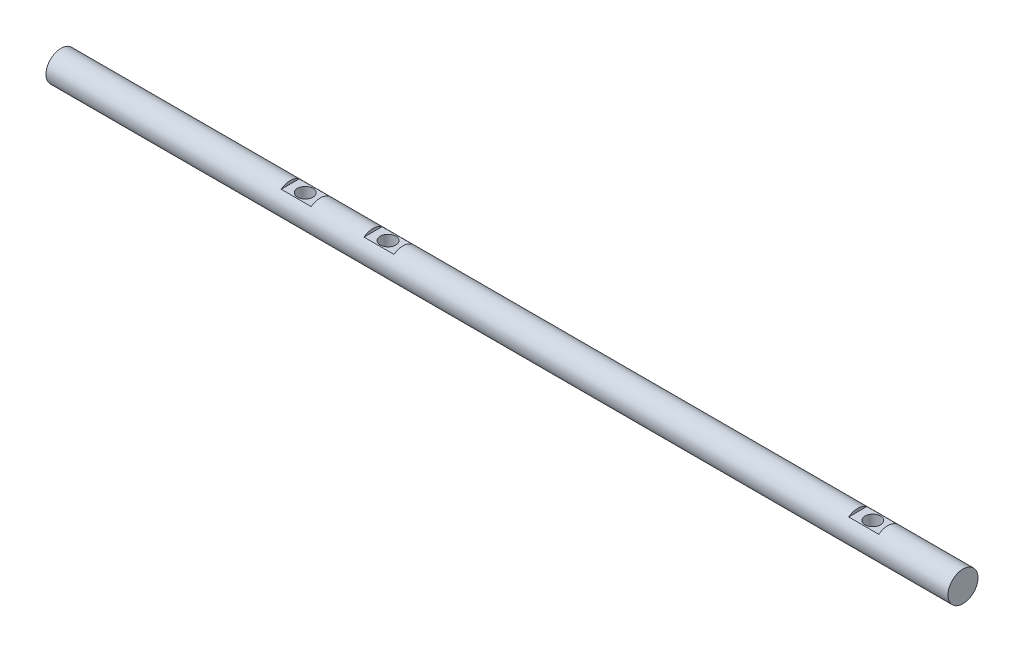
SolidWorks part; units mm, degrees
ref_plane "Front Plane" through (0, 0, 0) normal (0, 0, 1) x (1, 0, 0)
ref_plane "Top Plane" through (0, 0, 0) normal (0, 1, 0) x (1, 0, 0)
ref_plane "Right Plane" through (0, 0, 0) normal (1, 0, 0) x (0, 0, -1)
sketch "Sketch1" plane through (0, 0, 0) normal (1, 0, 0) x (0, 0, -1)
  circle A0 centre (0, 0) radius 3.175
  dimension "D1" = 6.35
extrude "Boss-Extrude1" add sketch "Sketch1" along normal blind 190.5
sketch "Sketch2" plane through (0, 0, 0) normal (0, 1, 0) x (1, 0, 0)
  line L0 (60.325, -3.175) -> (60.325, 3.175)
  line L1 (0, -3.175) -> (190.5, -3.175) construction
  line L2 (190.5, 3.175) -> (0, 3.175) construction
  line L3 (72.25, 5.8727) -> (65.9, 5.8727)
  line L4 (48.4, -5.8727) -> (54.75, -5.8727)
  line L5 (48.4, -5.8727) -> (48.4, 5.8727)
  line L6 (48.4, 5.8727) -> (54.75, 5.8727)
  line L7 (54.75, -5.8727) -> (54.75, 5.8727)
  line L8 (48.4, -5.8727) -> (54.75, 5.8727) construction
  line L9 (48.4, 5.8727) -> (54.75, -5.8727) construction
  line L10 (168.275, -7.2606) -> (174.625, -7.2606)
  line L11 (168.275, -7.2606) -> (168.275, 7.2606)
  line L12 (168.275, 7.2606) -> (174.625, 7.2606)
  line L13 (174.625, -7.2606) -> (174.625, 7.2606)
  line L14 (168.275, -7.2606) -> (174.625, 7.2606) construction
  line L15 (168.275, 7.2606) -> (174.625, -7.2606) construction
  line L16 (65.9, -5.8727) -> (65.9, 5.8727)
  line L17 (72.25, -5.8727) -> (65.9, -5.8727)
  line L18 (72.25, -5.8727) -> (72.25, 5.8727)
  circle A0 centre (171.45, 0) radius 1.632
  circle A1 centre (51.575, 0) radius 1.6319
  circle A2 centre (69.075, 0) radius 1.6319
  point P25 (0, 0)
  point P26 (173.364, 0)
  point P27 (176.9456, 15.8308)
  point P28 (166.3203, 14.8757)
  dimension "D1" = 3.2639
  dimension "D3" = 17.5
  dimension "D5" = 171.45
  dimension "D2" = 6.35
  dimension "D4" = 60.325
extrude "Cut-Extrude1" cut sketch "Sketch2" against normal through all both and the other way through all contours A1 | A2 | A0 region at (171.45, 0, 0) region at (51.575, 0, 0) region at (69.075, 0, 0)
extrude "Cut-Extrude2" cut sketch "Sketch2<3>" along normal through all from offset 2.54 contours L10 L13 L12 L11 A0 | L17 L18 L3 L16 A2 | L4 L7 L6 L5 A1 region at (72.1165, 0, 0) region at (48.5335, 0, 0) region at (168.4335, 0, 0)
sketch "Sketch2<3>" plane through (0, 0, 0) normal (0, 1, 0) x (1, 0, 0) same geometry as "Sketch2"
